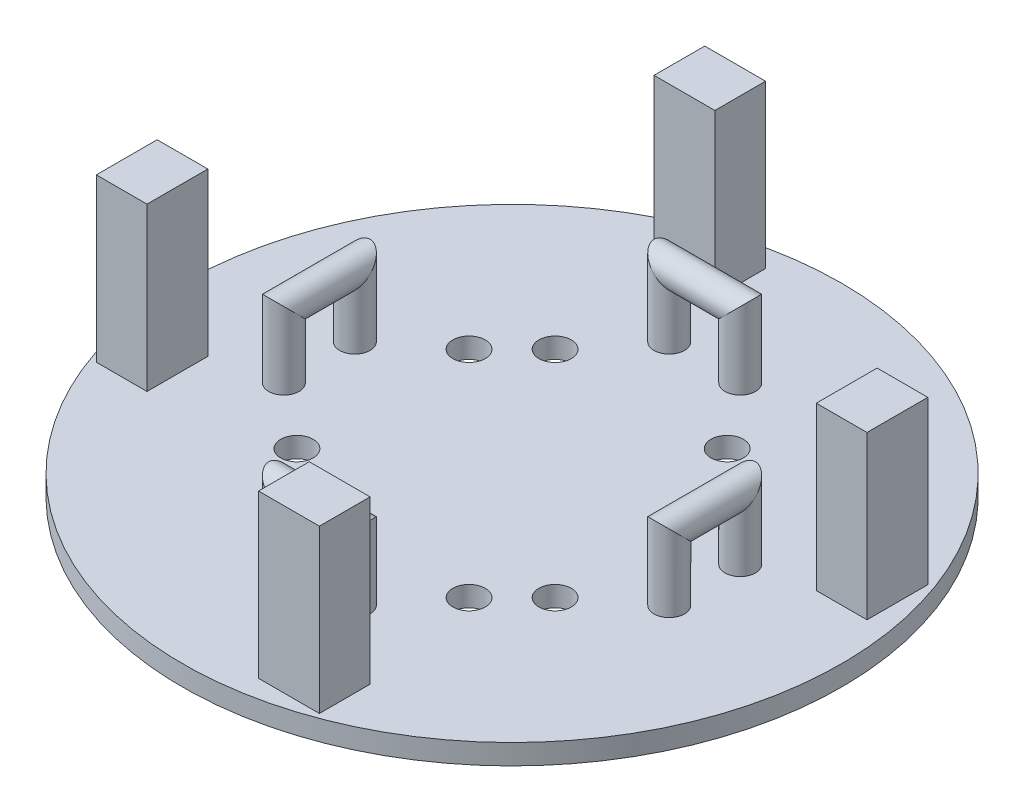
SolidWorks part; units mm, degrees
ref_plane "正面" through (0, 0, 0) normal (0, 0, 1) x (1, 0, 0)
ref_plane "平面" through (0, 0, 0) normal (0, 1, 0) x (1, 0, 0)
ref_plane "右側面" through (0, 0, 0) normal (1, 0, 0) x (0, 0, -1)
ref_plane "平面1" through (0, 0, 0) normal (-0.7071, 0.7071, 0) x (0.7071, 0.7071, 0)
sketch "ｽｹｯﾁ2" plane through (0, 0, 0) normal (0, 1, 0) x (1, 0, 0)
  circle A0 centre (3.5, 0) radius 1.5
  dimension "D2" = 3
  dimension "D1" = 3.5
extrude "ﾎﾞｽ - 押し出し1" add sketch "ｽｹｯﾁ2" along normal up to surface (14.5 mm away) up to plane "平面1"
sketch "ｽｹｯﾁ3" plane through (0, 0, 0) normal (1, 0, 0) x (0, 0, -1)
  circle A0 centre (0, 3.5) radius 1.5 construction
  circle A1 centre (0, 3.5) radius 1.5
extrude "ﾎﾞｽ - 押し出し2" add sketch "ｽｹｯﾁ3" along normal up to next
mirror "ﾐﾗｰ2" about plane through (0, 0, 0) normal (1, 0, 0) of bodies 102
sketch "ｽｹｯﾁ4" plane through (0, 0, 0) normal (0, -1, 0) x (1, 0, 0)
  circle A0 centre (3.5, 0) radius 1.5 construction
  circle A1 centre (-3.5, 0) radius 1.5 construction
  circle A2 centre (3.5, 0) radius 1.5
  circle A3 centre (-3.5, 0) radius 1.5
extrude "ﾎﾞｽ - 押し出し3" add sketch "ｽｹｯﾁ4" along normal blind 3
sketch "ｽｹｯﾁ5" plane through (0, -3, 0) normal (0, -1, 0) x (1, 0, 0)
  line L0 (-3.5, 0) -> (0, -19) construction
  line L1 (0, -19) -> (3.5, 0) construction
  circle A0 centre (0, -19) radius 32.5
  circle A1 centre (3.5, 0) radius 1.5 construction
  dimension "D1" = 19
  dimension "D2" = 65
extrude "ﾎﾞｽ - 押し出し4" add sketch "ｽｹｯﾁ5" along normal blind 2
ref_axis "軸1" through (0, -5, -19) along (0, 1, 0)
pattern_circular "円形ﾊﾟﾀｰﾝ2" count 4 over 360 about axis through (0, -5, -19) along (0, 1, 0) of bodies 105
sketch "ｽｹｯﾁ6" plane through (0, -3, 0) normal (0, 1, 0) x (1, 0, 0)
  line L1 (30, 30) -> (25, 30)
  line L2 (30, 30) -> (30, 24)
  line L3 (30, 24) -> (25, 24)
  line L4 (25, 30) -> (25, 24)
  line L5 (30, 30) -> (25, 24) construction
  line L6 (30, 24) -> (25, 30) construction
  circle A0 centre (0, 19) radius 32.5 construction
  circle A1 centre (19, 22.5) radius 1.5 construction
  point P0 (27.5, 27)
  dimension "D1" = 5
  dimension "D2" = 6
  dimension "D3" = 5
  dimension "D4" = 6
extrude "ﾎﾞｽ - 押し出し5" add sketch "ｽｹｯﾁ6" along normal blind 16
pattern_circular "円形ﾊﾟﾀｰﾝ3" count 4 over 360 about axis through (0, -3, -19) along (0, -1, 0) of "ﾎﾞｽ - 押し出し5"
sketch "ｽｹｯﾁ7" plane through (0, -3, 0) normal (0, 1, 0) x (1, 0, 0)
  line L0 (0, 19) -> (-22.981, -3.981) construction
  line L1 (3.5, 1.5) -> (-3.5, 1.5) construction
  line L2 (-8.4853, 6.2721) -> (-10.6066, 8.3934) construction
  circle A0 centre (0, 19) radius 32.5 construction
  circle A1 centre (-8.4853, 6.2721) radius 1.6
  circle A2 centre (-12.7279, 10.5147) radius 1.6
  dimension "D2" = 3
  dimension "D3" = 15
  dimension "D4" = 3.2
  dimension "D1" = 45
extrude "ｶｯﾄ - 押し出し1" cut sketch "ｽｹｯﾁ7" against normal through all
pattern_circular "円形ﾊﾟﾀｰﾝ4" count 4 over 360 about axis through (0, -3, -19) along (0, -1, 0) of "ｶｯﾄ - 押し出し1"
